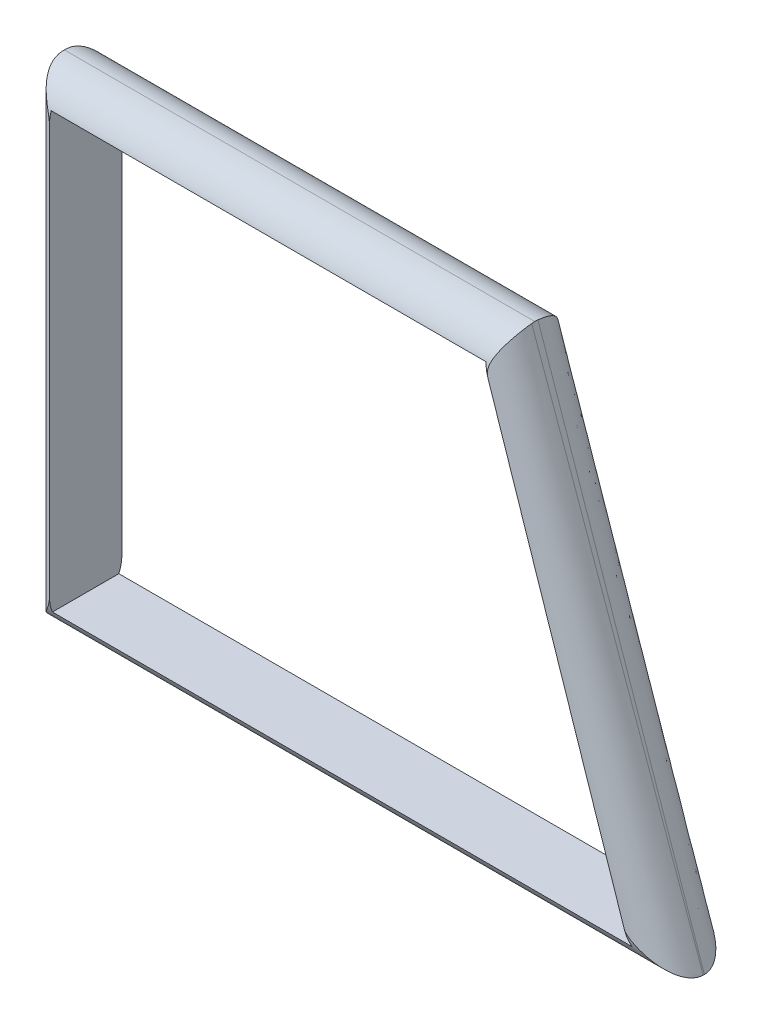
SolidWorks part; units mm, degrees
ref_plane "Front Plane" through (0, 0, 0) normal (0, 0, 1) x (1, 0, 0)
ref_plane "Top Plane" through (0, 0, 0) normal (0, 1, 0) x (1, 0, 0)
ref_plane "Right Plane" through (0, 0, 0) normal (1, 0, 0) x (0, 0, -1)
sketch "Sketch1" plane through (0, 0, 0) normal (0, 0, 1) x (1, 0, 0)
  line L0 (0.3463, 0.3544) -> (0.5797, -0.3099)
  line L1 (-0.3029, 0.3544) -> (0.3463, 0.3544)
  line L2 (-0.3029, 0.3544) -> (-0.3029, -0.3099)
  line L3 (-0.3029, -0.3099) -> (0.2649, -0.3099)
  line L4 (-0.2736, -0.2799) -> (-0.2736, 0.3201)
  line L5 (-0.3029, 0.3544) -> (0.2649, -0.3099) construction
  line L6 (-0.3029, -0.3099) -> (0.3463, 0.3544) construction
  line L8 (-0.2736, 0.3201) -> (0.3264, 0.3201)
  line L9 (0.3264, 0.3201) -> (0.5264, -0.2799)
  line L10 (0.5264, -0.2799) -> (-0.2736, -0.2799)
  line L11 (0.5797, -0.3099) -> (0.2649, -0.3099)
  point P0 (0, 0)
  point P6 (0.5797, -0.3099)
  point P12 (0, 0)
  dimension "D1" = 0.6
  dimension "D2" = 0.8
  dimension "D3" = 0.6
  dimension "D4" = 0.0293
  dimension "D5" = 0.0343
  dimension "D6" = 0.03
extrude "Boss-Extrude2" add sketch "Sketch1" along normal mid plane 0.1
fillet "Fillet23" radius 0.05 2 edges at (0.0217, 0.3544, -0.05) (0.0217, 0.3544, 0.05) tangent propagation no
fillet "Fillet25" radius 0.05 2 edges at (0.1384, -0.3099, 0.05) (0.1384, -0.3099, -0.05) tangent propagation no
fillet "Fillet26" radius 0.05 2 edges at (-0.3029, 0.0222, 0.05) (-0.3029, 0.0222, -0.05) tangent propagation no
fillet "Fillet27" radius 0.05 2 edges at (0.463, 0.0222, -0.05) (0.463, 0.0222, 0.05) tangent propagation no
